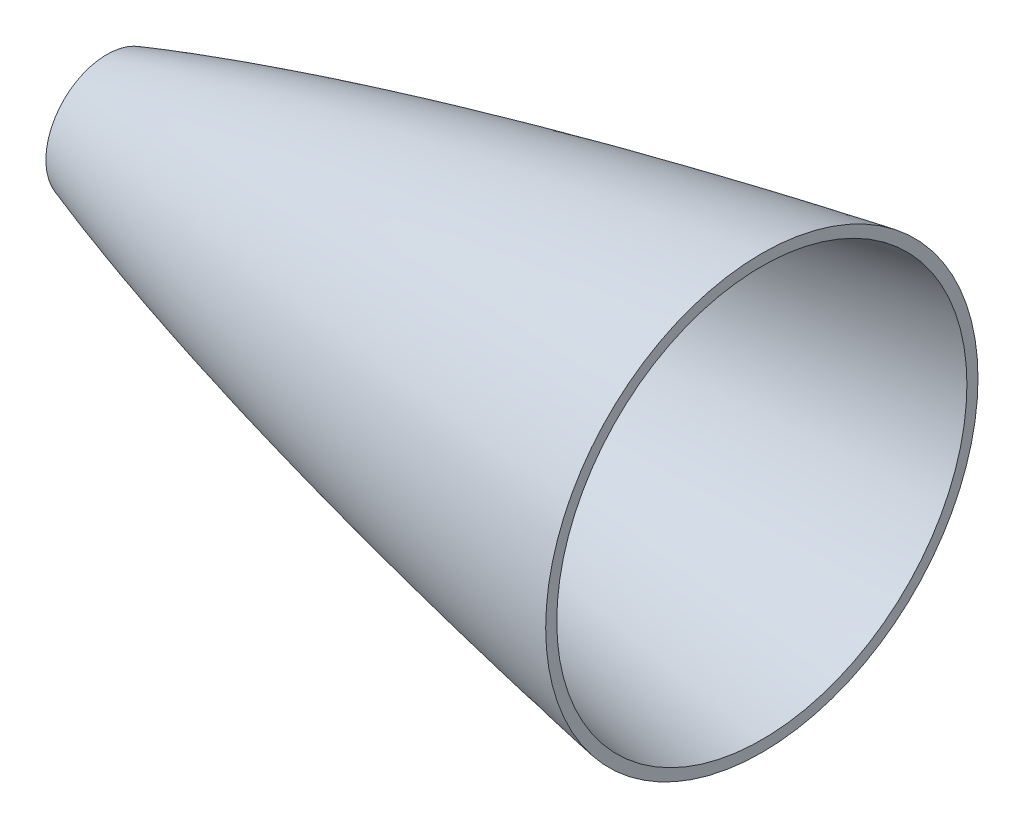
SolidWorks part; units mm, degrees
ref_plane "Front Plane" through (0, 0, 0) normal (0, 0, 1) x (1, 0, 0)
ref_plane "Top Plane" through (0, 0, 0) normal (0, 1, 0) x (1, 0, 0)
ref_plane "Right Plane" through (0, 0, 0) normal (1, 0, 0) x (0, 0, -1)
sketch "Sketch1" plane through (0, 0, 0) normal (0, 0, 1) x (1, 0, 0)
  line L0 (0, 0) -> (457.2, 0) construction
  line L1 (0, 0) -> (0, 88.9) construction
  line L2 (457.2, 88.9151) -> (457.2, 0) construction
  line L3 (457.2, 0) -> (0, 0)
  line L5 (457.2, 0) -> (469.9, 0)
  line L7 (457.2, 88.9151) -> (469.9, 88.9151)
  line L8 (469.9, 0) -> (469.9, 88.9151)
  spline S0 degree 4 poles (0, 0) (0.0023, 0.0117) (0.0082, 0.0346) (0.0259, 0.0787) (0.0695, 0.163) (0.1339, 0.2631) (0.2191, 0.3779) (0.3369, 0.5207) (0.5082, 0.71) (0.7967, 0.9964) (1.2973, 1.4371) (2.1712, 2.1158) (3.7004, 3.1565) (6.4155, 4.7689) (11.1356, 7.1992) (18.8819, 10.6607) (32.1609, 15.8309) (51.2281, 22.2453) (75.2291, 29.3426) (102.987, 36.6637) (131.6184, 43.5191) (160.3731, 49.8355) (189.2264, 55.6835) (218.1627, 61.1047) (247.1713, 66.1244) (276.2447, 70.7536) (305.3776, 74.9923) (334.5665, 78.8281) (363.8087, 82.2339) (389.4414, 84.7941) (411.4449, 86.6328) (428.6333, 87.7894) (439.7384, 88.3858) (448.4262, 88.7338) (453.4393, 88.8671) (455.9463, 88.9096) (457.2, 88.9151) knots 0 0 0 0 0 0.000101 0.000202 0.000405 0.000809 0.001116 0.001422 0.001985 0.002988 0.004584 0.007113 0.011426 0.01877 0.031526 0.052412 0.083828 0.140383 0.203215 0.266046 0.328877 0.391708 0.454539 0.51737 0.580202 0.643033 0.705864 0.768695 0.831526 0.894357 0.925773 0.957189 0.978594 0.989297 1 1 1 1 1 construction
  spline S1 degree 4 poles (0, 0) (0.0023, 0.0117) (0.0082, 0.0346) (0.0259, 0.0787) (0.0695, 0.163) (0.1339, 0.2631) (0.2191, 0.3779) (0.3369, 0.5207) (0.5082, 0.71) (0.7967, 0.9964) (1.2973, 1.4371) (2.1712, 2.1158) (3.7004, 3.1565) (6.4155, 4.7689) (11.1356, 7.1992) (18.8819, 10.6607) (32.1609, 15.8309) (51.2281, 22.2453) (75.2291, 29.3426) (102.987, 36.6637) (131.6184, 43.5191) (160.3731, 49.8355) (189.2264, 55.6835) (218.1627, 61.1047) (247.1713, 66.1244) (276.2447, 70.7536) (305.3776, 74.9923) (334.5665, 78.8281) (363.8087, 82.2339) (389.4414, 84.7941) (411.4449, 86.6328) (428.6333, 87.7894) (439.7384, 88.3858) (448.4262, 88.7338) (453.4393, 88.8671) (455.9463, 88.9096) (457.2, 88.9151) knots 0 0 0 0 0 0.000101 0.000202 0.000405 0.000809 0.001116 0.001422 0.001985 0.002988 0.004584 0.007113 0.011426 0.01877 0.031526 0.052412 0.083828 0.140383 0.203215 0.266046 0.328877 0.391708 0.454539 0.51737 0.580202 0.643033 0.705864 0.768695 0.831526 0.894357 0.925773 0.957189 0.978594 0.989297 1 1 1 1 1
  dimension "D1" = 457.2
  dimension "D2" = 88.9
  dimension "D3" = 12.7
revolve "Revolve1" add sketch "Sketch1" angle 360 about L3
shell "Shell1" thickness 3.175 removed face at (469.9, 0, -88.9151)
sketch "Sketch3" plane through (469.9, 0, 0) normal (1, 0, 0) x (0, 0, -1)
  circle A0 centre (6.3909, 85.5016) radius 245.9036
  circle A1 centre (0, 0) radius 85.7401 construction
extrude "Cut-Extrude1" cut sketch "Sketch3" against normal blind 241.3
sketch "Sketch4" plane through (0, 0, 0) normal (1, 0, 0) x (0, 0, -1)
  circle A0 centre (0, 0) radius 81.6752
extrude "Cut-Extrude2" cut sketch "Sketch4" along normal blind 38.1
